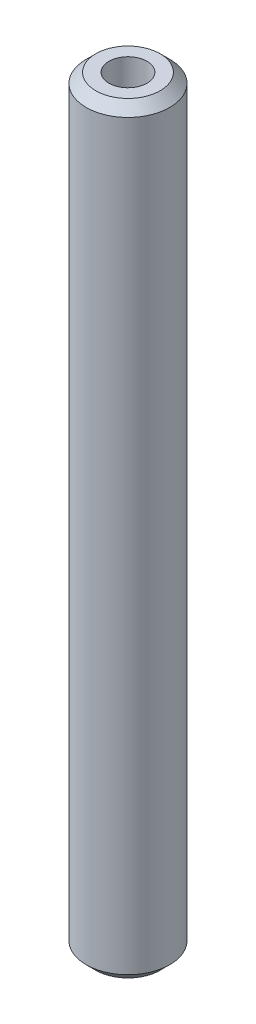
SolidWorks part; units mm, degrees
ref_plane "Front Plane" through (0, 0, 0) normal (0, 0, 1) x (1, 0, 0)
ref_plane "Top Plane" through (0, 0, 0) normal (0, 1, 0) x (1, 0, 0)
ref_plane "Right Plane" through (0, 0, 0) normal (1, 0, 0) x (0, 0, -1)
sketch "Sketch1" plane through (0, 0, 0) normal (0, 1, 0) x (1, 0, 0)
  circle A0 centre (0, 0) radius 10
  dimension "SHAFT_OD" = 20
extrude "Boss-Extrude1" add sketch "Sketch1" along normal blind 182.3119
sketch "Sketch2" plane through (0, 0, 0) normal (0, 1, 0) x (1, 0, 0)
  circle A0 centre (0, 0) radius 4.5571
  dimension "BORE_D" = 9.1143
extrude "Cut-Extrude1" cut sketch "Sketch2" along normal through all
chamfer "Chamfer1" distance 2.3078 angle 45 2 edges at (0, 182.3119, 10) (0, 0, 10)
